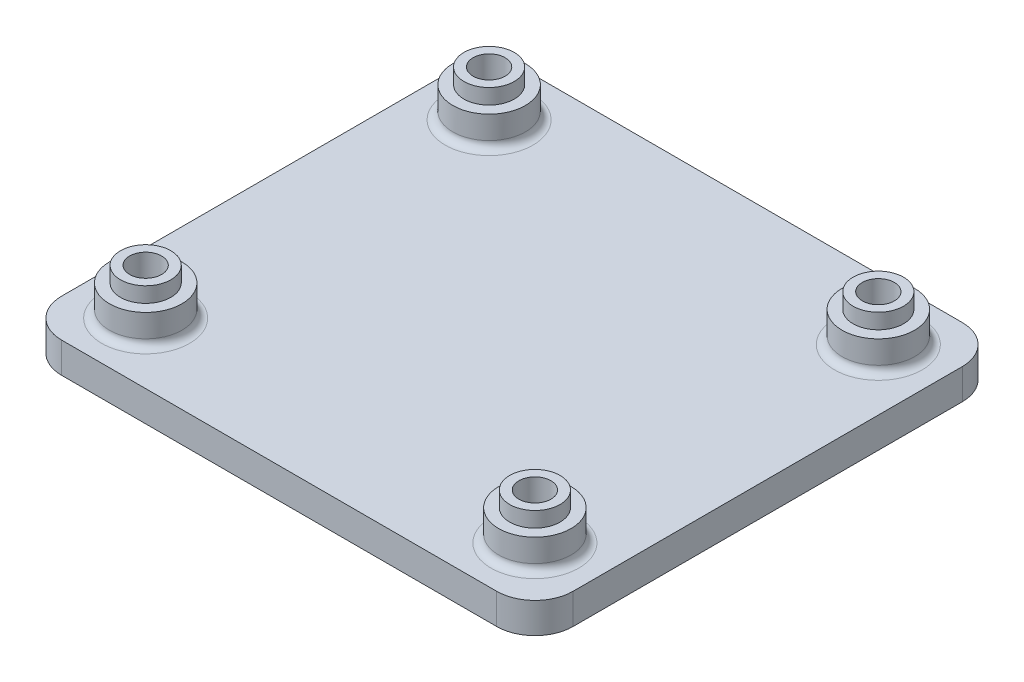
SolidWorks part; units mm, degrees
ref_plane "Plan de face" through (0, 0, 0) normal (0, 0, 1) x (1, 0, 0)
ref_plane "Plan de dessus" through (0, 0, 0) normal (0, 1, 0) x (1, 0, 0)
ref_plane "Plan de droite" through (0, 0, 0) normal (1, 0, 0) x (0, 0, -1)
sketch "Esquisse1" plane through (0, 0, 0) normal (0, 1, 0) x (1, 0, 0)
  line L1 (0, 0) -> (67, 0)
  line L2 (0, 0) -> (0, 61)
  line L3 (0, 61) -> (67, 61)
  line L4 (67, 0) -> (67, 61)
  dimension "D1" = 67
  dimension "D2" = 61
extrude "Boss.-Extru.1" add sketch "Esquisse1" along normal blind 4
sketch "Esquisse4" plane through (0, 4, 0) normal (0, 1, 0) x (1, 0, 0)
  line L0 (0, 61) -> (0, 0) construction
  line L1 (0, 0) -> (67, 0) construction
  circle A0 centre (8, 8) radius 4.75
  circle A1 centre (8, 53) radius 4.75
  circle A2 centre (59, 8) radius 4.75
  circle A3 centre (59, 53) radius 4.75
  dimension "D1" = 9.5
  dimension "D2" = 9.5
  dimension "D3" = 9.5
  dimension "D4" = 9.5
  dimension "D5" = 45
  dimension "D6" = 51
  dimension "D7" = 51
  dimension "D8" = 45
  dimension "D9" = 8
  dimension "D10" = 8
  dimension "D11" = 8
  dimension "D12" = 8
extrude "Boss.-Extru.3" add sketch "Esquisse4" along normal blind 4
sketch "Esquisse5" plane through (0, 8, 0) normal (0, 1, 0) x (1, 0, 0)
  circle A0 centre (59, 53) radius 3.3
  circle A1 centre (59, 8) radius 3.3
  circle A2 centre (8, 8) radius 3.3
  circle A3 centre (8, 53) radius 3.3
  dimension "D1" = 6.6
  dimension "D2" = 6.6
  dimension "D3" = 6.6
  dimension "D4" = 6.6
extrude "Boss.-Extru.4" add sketch "Esquisse5" along normal blind 2
sketch "Esquisse6" plane through (0, 10, 0) normal (0, 1, 0) x (1, 0, 0)
  circle A0 centre (8, 8) radius 2.1
  circle A1 centre (8, 53) radius 2.1
  circle A2 centre (59, 53) radius 2.1
  circle A3 centre (59, 8) radius 2.1
  dimension "D1" = 4.2
  dimension "D2" = 4.2
  dimension "D3" = 4.2
  dimension "D4" = 4.2
extrude "Enlèv. mat.-Extru.2" cut sketch "Esquisse6" against normal through all
fillet "Congé2" radius 1 4 edges at (59, 4, -57.75) (8, 4, -57.75) (8, 4, -12.75) (59, 4, -12.75)
fillet "Congé3" radius 5 4 edges at (0, 2, -61) (0, 2, 0) (67, 2, 0) (67, 2, -61)
